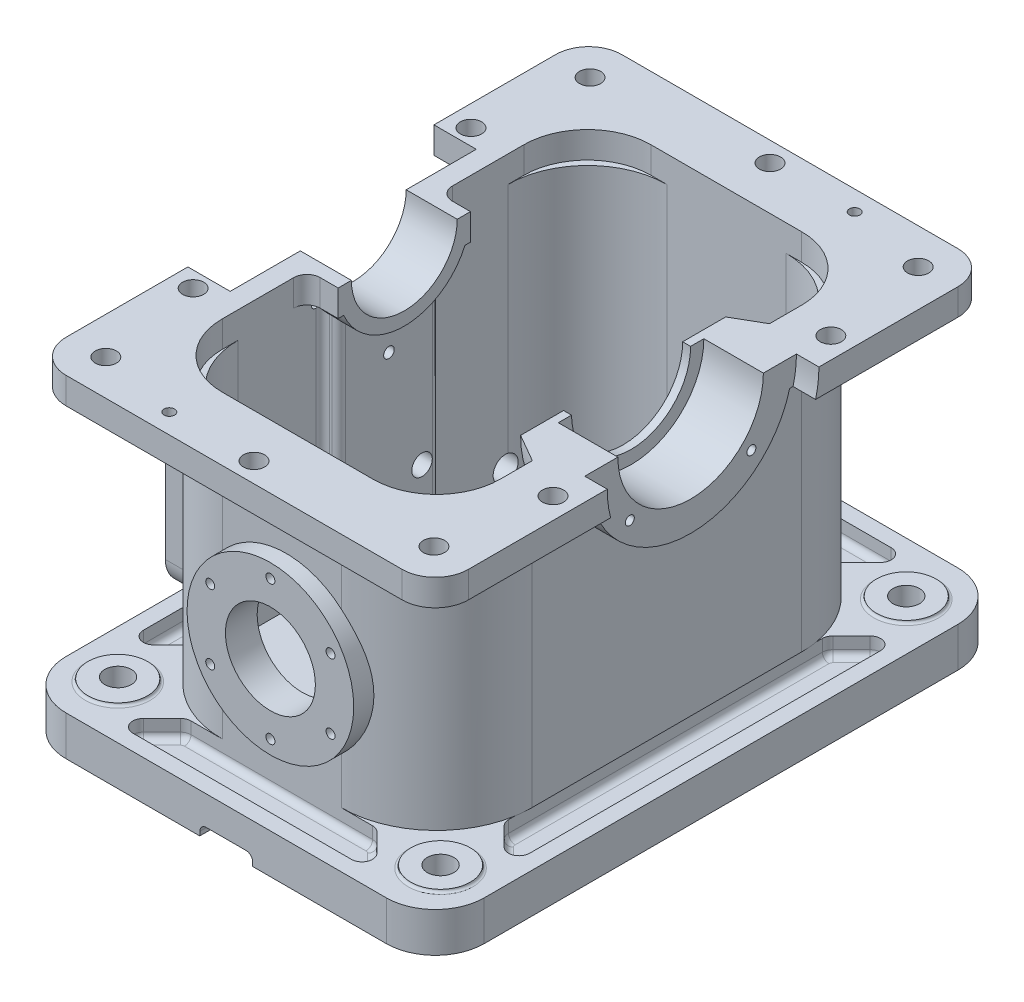
SolidWorks part; units mm, degrees
note: The reader was unsure of these and kept them because the rebuilt part matched: shared geometry of "草图44<2>".
ref_plane "前视基准面" through (0, 0, 0) normal (0, 0, 1) x (1, 0, 0)
ref_plane "上视基准面" through (0, 0, 0) normal (0, 1, 0) x (1, 0, 0)
ref_plane "右视基准面" through (0, 0, 0) normal (1, 0, 0) x (0, 0, -1)
sketch "草图1" plane through (0, 0, 0) normal (0, 1, 0) x (1, 0, 0)
  line L0 (0, 0) -> (316, 0)
  line L1 (316, 0) -> (316, 432)
  line L2 (316, 432) -> (0, 432)
  line L3 (0, 432) -> (0, 0)
extrude "凸台-拉伸1" add sketch "草图1" along normal blind 30
sketch "草图2" plane through (0, 30, 0) normal (0, 1, 0) x (1, 0, 0)
  circle A0 centre (36, 40) radius 22.5
  circle A1 centre (36, 392) radius 22.5
  circle A2 centre (280, 392) radius 22.5
  circle A3 centre (280, 40) radius 22.5
  point P12 (280, 0)
  point P13 (280, 432)
  point P14 (36, 0)
  point P15 (36, 432)
  point P16 (0, 40)
  point P17 (316, 40)
  point P18 (0, 392)
  point P19 (316, 392)
extrude "凸台-拉伸2" add sketch "草图2" along normal blind 2
sketch "草图3" plane through (0, 32, 0) normal (0, 1, 0) x (1, 0, 0)
  circle A0 centre (35.0597, 41.1667) radius 10
  circle A1 centre (36, 392) radius 10
  circle A2 centre (280, 40) radius 10
  circle A3 centre (280, 392) radius 10
extrude "切除-拉伸1" cut sketch "草图3" against normal through all
fillet "圆角1" radius 37 4 edges at (0, 15, -432) (0, 15, 0) (316, 15, 0) (316, 15, -432)
fillet "圆角3" radius 2 4 edges at (280, 30, -62.5) (36, 30, -17.5) (280, 30, -369.5) (36, 30, -414.5)
sketch "草图4" plane through (0, 30, 0) normal (0, 1, 0) x (1, 0, 0)
  line L0 (42, 334.603) -> (42, 97.397)
  line L1 (246.2599, 406.3431) -> (232.2599, 392.3431)
  line L2 (12, 348.603) -> (12, 83.397)
  line L3 (290.3431, 354.2599) -> (276.3431, 340.2599)
  line L4 (304, 348.603) -> (304, 83.397)
  line L5 (240.603, 420) -> (75.397, 420)
  line L6 (187.4957, 390) -> (187.4957, 390)
  line L7 (25.6569, 354.2599) -> (39.6569, 340.2599)
  line L8 (226.603, 390) -> (89.397, 390)
  line L9 (274, 334.603) -> (274, 97.397)
  line L10 (69.7401, 406.3431) -> (83.7401, 392.3431)
  line L11 (187.4957, 390) -> (37, 390) construction
  line L12 (246.2599, 406.3431) -> (209.0421, 369.1254) construction
  line L13 (226.603, 42) -> (89.397, 42)
  line L14 (304, 395) -> (304, 37) construction
  line L15 (274, 395) -> (274, 37) construction
  line L16 (316, 216) -> (0, 216) construction
  line L17 (316, 37) -> (316, 395) construction
  line L18 (0, 395) -> (0, 37) construction
  line L19 (158, 432) -> (158, 0) construction
  line L20 (279, 432) -> (37, 432) construction
  line L21 (37, 0) -> (279, 0) construction
  line L22 (240.603, 12) -> (75.397, 12)
  line L23 (69.7401, 25.6569) -> (83.7401, 39.6569)
  line L24 (240.603, 420) -> (37, 420) construction
  line L25 (290.3431, 77.7401) -> (276.3431, 91.7401)
  line L26 (246.2599, 25.6569) -> (232.2599, 39.6569)
  line L27 (25.6569, 77.7401) -> (39.6569, 91.7401)
  arc A0 (246.2599, 406.3431) -> (240.603, 420) centre (240.603, 412) ccw
  arc A1 (187.4957, 390) -> (187.4957, 390) centre (187.4957, 390) ccw
  arc A2 (232.2599, 392.3431) -> (226.603, 390) centre (226.603, 398) cw
  arc A3 (290.3431, 354.2599) -> (304, 348.603) centre (296, 348.603) cw
  arc A4 (276.3431, 340.2599) -> (274, 334.603) centre (282, 334.603) ccw
  arc A5 (39.6569, 340.2599) -> (42, 334.603) centre (34, 334.603) cw
  arc A6 (25.6569, 354.2599) -> (12, 348.603) centre (20, 348.603) ccw
  arc A7 (83.7401, 392.3431) -> (89.397, 390) centre (89.397, 398) ccw
  arc A8 (69.7401, 406.3431) -> (75.397, 420) centre (75.397, 412) cw
  arc A9 (69.7401, 25.6569) -> (75.397, 12) centre (75.397, 20) ccw
  arc A10 (83.7401, 39.6569) -> (89.397, 42) centre (89.397, 34) cw
  arc A11 (276.3431, 91.7401) -> (274, 97.397) centre (282, 97.397) cw
  arc A12 (290.3431, 77.7401) -> (304, 83.397) centre (296, 83.397) ccw
  arc A13 (232.2599, 39.6569) -> (226.603, 42) centre (226.603, 34) ccw
  arc A14 (246.2599, 25.6569) -> (240.603, 12) centre (240.603, 20) cw
  arc A15 (25.6569, 77.7401) -> (12, 83.397) centre (20, 83.397) cw
  arc A16 (39.6569, 91.7401) -> (42, 97.397) centre (34, 97.397) ccw
  point P24 (42, 216)
  point P46 (304, 216)
  point P48 (158, 420)
  point P54 (158, 390)
  point P56 (274, 216)
  point P78 (12, 216)
  dimension "D6" = 8
  dimension "D7" = 8
  dimension "D8" = 8
  dimension "D9" = 8
  dimension "D3" = 30
  dimension "D4" = 30
extrude "切除-拉伸2" cut sketch "草图4" against normal blind 14 contours A14 L26 A13 L13 A10 L23 A9 L22 | L27 A16 L0 A5 L7 A6 L2 A15 | L5 A8 L10 A7 L8 A2 L1 A0 | L9 A11 L25 A12 L4 A3 L3 A4
fillet "圆角4" radius 5 32 edges at (16.9385, 16, -76.0059) (12, 16, -216) (16.9385, 16, -355.9941) (32.6569, 16, -347.2599) (41.391, 16, -337.6645) (42, 16, -216) (41.391, 16, -94.3355) (32.6569, 16, -84.7401) (158, 16, -12) (68.0059, 16, -16.9385) (76.7401, 16, -32.6569) (86.3355, 16, -41.391) (158, 16, -42) (229.6645, 16, -41.391) (239.2599, 16, -32.6569) (247.9941, 16, -16.9385) (283.3431, 16, -347.2599) (299.0615, 16, -355.9941) (304, 16, -216) (299.0615, 16, -76.0059) (283.3431, 16, -84.7401) (274.609, 16, -94.3355) (274, 16, -216) (274.609, 16, -337.6645) (239.2599, 16, -399.3431) (229.6645, 16, -390.609) (158, 16, -390) (86.3355, 16, -390.609) (76.7401, 16, -399.3431) (68.0059, 16, -415.0615) (158, 16, -420) (247.9941, 16, -415.0615)
ref_plane "基准面1" through (0, 225, 0) normal (0, -1, 0) x (1, 0, 0)
sketch "草图5" plane through (0, 225, 0) normal (0, -1, 0) x (1, 0, 0)
  line L0 (158, -432) -> (158, 0) construction
  line L1 (279, -432) -> (37, -432) construction
  line L2 (37, 0) -> (279, 0) construction
  line L3 (0, -216) -> (316, -216) construction
  line L4 (0, -395) -> (0, -37) construction
  line L5 (316, -37) -> (316, -395) construction
  line L6 (263, -330) -> (263, -303.5)
  line L7 (53, -330) -> (53, -276)
  line L8 (101, -378) -> (215, -378)
  line L9 (101, -54) -> (215, -54)
  line L10 (6, -401) -> (6, -31)
  line L11 (31, -426) -> (285, -426)
  line L12 (310, -401) -> (310, -31)
  line L13 (31, -6) -> (285, -6)
  line L14 (53, -432) -> (53, 0) construction
  line L15 (0, -378) -> (316, -378) construction
  line L16 (263, -303.5) -> (242, -287.75)
  line L17 (0, -54) -> (316, -54) construction
  line L18 (242, -287.75) -> (242, -144.25)
  line L19 (263, -102) -> (263, -128.5)
  line L20 (263, -128.5) -> (242, -144.25)
  line L21 (76.6, -266) -> (63, -266)
  line L22 (101, -357) -> (215, -357) construction
  line L23 (74, -330) -> (74, -102) construction
  line L24 (101, -75) -> (215, -75) construction
  line L25 (242, -330) -> (242, -102) construction
  line L26 (76.6, -166) -> (76.6, -266)
  line L27 (76.6, -166) -> (63, -166)
  line L28 (263, -330) -> (263, -102) construction
  line L29 (53, -156) -> (53, -102)
  line L31 (53, -330) -> (53, -102) construction
  arc A1 (6, -401) -> (31, -426) centre (31, -401) ccw
  arc A2 (31, -6) -> (6, -31) centre (31, -31) ccw
  arc A3 (285, -6) -> (310, -31) centre (285, -31) cw
  arc A4 (310, -401) -> (285, -426) centre (285, -401) cw
  arc A5 (53, -330) -> (101, -378) centre (101, -330) ccw
  arc A6 (263, -330) -> (215, -378) centre (215, -330) cw
  arc A7 (215, -54) -> (263, -102) centre (215, -102) cw
  arc A8 (53, -102) -> (101, -54) centre (101, -102) cw
  arc A9 (53, -276) -> (63, -266) centre (63, -276) cw
  arc A10 (53, -156) -> (63, -166) centre (63, -156) ccw
  arc A13 (242, -330) -> (215, -357) centre (215, -330) cw construction
  arc A14 (74, -330) -> (101, -357) centre (101, -330) ccw construction
  arc A15 (74, -102) -> (101, -75) centre (101, -102) cw construction
  arc A16 (215, -75) -> (242, -102) centre (215, -102) cw construction
  point P65 (76.6, -216)
  point P74 (53, -166)
  dimension "D5" = 25
  dimension "D6" = 25
  dimension "D7" = 25
  dimension "D8" = 25
  dimension "D9" = 48
  dimension "D10" = 48
  dimension "D11" = 48
  dimension "D12" = 48
  dimension "D14" = 10
  dimension "D15" = 10
  dimension "D2" = 105
  dimension "D3" = 162
  dimension "D4" = 162
  dimension "D13" = 21
extrude "凸台-拉伸3" add sketch "草图5" against normal blind 20 separate body
sketch "草图6" plane through (0, 30, 0) normal (0, 1, 0) x (1, 0, 0)
  line L1 (263, 202) -> (263, 230)
  line L2 (65, 183) -> (65, 216)
  line L3 (65, 216) -> (65, 249)
  line L4 (60, 178) -> (58, 178)
  line L5 (60, 254) -> (58, 254)
  line L6 (53, 173) -> (53, 114)
  line L7 (113, 54) -> (203, 54)
  line L8 (263, 202) -> (263, 114)
  line L28 (275, 318) -> (275, 114)
  line L29 (113, 390) -> (203, 390)
  line L30 (41, 318) -> (41, 114)
  line L31 (113, 42) -> (203, 42)
  line L42 (263, 318) -> (263, 230)
  line L43 (113, 378) -> (203, 378)
  line L44 (53, 318) -> (53, 259)
  arc A0 (53, 114) -> (113, 54) centre (113, 114) ccw
  arc A1 (203, 54) -> (263, 114) centre (203, 114) ccw
  arc A2 (58, 254) -> (53, 259) centre (58, 259) cw
  arc A4 (60, 254) -> (65, 249) centre (60, 249) cw
  arc A5 (65, 183) -> (60, 178) centre (60, 183) cw
  arc A6 (53, 173) -> (58, 178) centre (58, 173) cw
  arc A20 (203, 42) -> (275, 114) centre (203, 114) ccw
  arc A21 (275, 318) -> (203, 390) centre (203, 318) ccw
  arc A22 (41, 318) -> (113, 390) centre (113, 318) cw
  arc A23 (41, 114) -> (113, 42) centre (113, 114) ccw
  arc A34 (263, 318) -> (203, 378) centre (203, 318) ccw
  arc A35 (53, 318) -> (113, 378) centre (113, 318) cw
  point P15 (251, 318)
  point P16 (251, 114)
  point P21 (65, 114)
  point P22 (65, 318)
  point P24 (0, 216)
  point P25 (316, 216)
  point P30 (0, 225)
  point P31 (316, 225)
  point P32 (0, 207)
  point P33 (316, 207)
  point P34 (235, 318)
  point P35 (235, 114)
  point P45 (251, 207)
  point P48 (77, 318)
  point P49 (77, 114)
  point P50 (53, 182)
  point P51 (316, 182)
  point P52 (53, 250)
  point P53 (316, 250)
  dimension "D3" = 5
ref_plane "基准面2" through (-5, 0, 0) normal (1, 0, 0) x (0, 0, -1)
sketch "草图7" plane through (-5, 0, 0) normal (1, 0, 0) x (0, 0, -1)
  circle A0 centre (316, 40) radius 17.5
  point P5 (432, 40)
  point P6 (261.659, 40)
  point P9 (316, 0)
  point P10 (316, 75.4539)
sketch "草图10" plane through (0, 0, 0) normal (-1, 0, 0) x (0, 0, 1)
  line L0 (-254, 30) -> (-249.5892, 36.1038)
  line L1 (-249.5892, 36.1038) -> (-182.0723, 36.1038)
  line L2 (-182.0723, 36.1038) -> (-178, 30)
  line L3 (-178, 30) -> (-178.4878, 30.1375)
  line L4 (-254, 25) -> (-178, 25)
  line L5 (-178, 25) -> (-178, 30)
  line L6 (-254, 25) -> (-254, 30)
  point P0 (-216, 0)
  point P1 (-216, 30)
  point P6 (-293.5905, 30)
  point P7 (-134.5219, 30)
  point P8 (-293.5905, 25)
  point P9 (-134.5219, 25)
  point P12 (-254, 0)
extrude "凸台-拉伸28" add sketch "草图6" along normal blind 195
ref_plane "基准面6" through (12, 30, -348.603) normal (0, 0, 1) x (1, 0, 0)
extrude "凸台-拉伸29" add sketch "草图7" along normal up to next
sketch "草图29" plane through (-5, 0, 0) normal (-1, 0, 0) x (0, 0, 1)
  point P0 (-316, 40)
hole_wizard "M20X1.5 螺纹孔的螺纹孔钻头2" positions "3D草图4" profile "草图30" hole size "M20X1.5" standard "GB"
sketch3d "3D草图4"
  point P0 (-5, 40, -316)
sketch "草图30" plane through (-5, 40, -316) normal (0, 1, 0) x (0, 0, 1)
  line L0 (0, 0) -> (0, 65.558)
  line L1 (0, 65.558) -> (9.25, 60)
  line L2 (9.25, 60) -> (9.25, 0)
  line L5 (9.25, 0) -> (0, 0)
  line L10 (0, 65.558) -> (-9.25, 60) construction
  line L11 (0, -6.35) -> (0, 107.95) construction
  dimension "孔直径" = 18.5
  dimension "孔深度" = 60
  dimension "导头角度" = 118
sketch "草图44" plane through (0, 0, -42) normal (0, 0, 1) x (1, 0, 0)
  circle A0 centre (161.3772, 112.6617) radius 63
extrude "凸台-拉伸31" add sketch "草图44" along normal blind 12
extrude "凸台-拉伸32" add sketch "草图44<2>" against normal up to next (12 mm away)
sketch "草图44<2>" plane through (0, 0, -42) normal (0, 0, 1) x (1, 0, 0) same geometry as "草图44"
sketch "草图45" plane through (0, 0, -30) normal (0, 0, 1) x (1, 0, 0)
  circle A0 centre (161.3772, 112.6617) radius 34
extrude "切除-拉伸13" cut sketch "草图45" against normal up to next
sketch "草图46" plane through (0, 0, -30) normal (0, 0, 1) x (1, 0, 0)
  point P3 (161.3772, 165.1617)
hole_wizard "M8 螺纹孔的螺纹孔钻头3" positions "3D草图5" profile "草图47" hole size "M8" standard "GB"
sketch3d "3D草图5"
  point P0 (161.3772, 165.1617, -30)
sketch "草图47" plane through (161.3772, 165.1617, -30) normal (1, 0, 0) x (0, -1, 0)
  line L0 (0, 0) -> (0, 17.0429)
  line L1 (0, 17.0429) -> (3.4, 15)
  line L2 (3.4, 15) -> (3.4, 0)
  line L5 (3.4, 0) -> (0, 0)
  line L10 (0, 17.0429) -> (-3.4, 15) construction
  line L11 (0, -6.35) -> (0, 107.95) construction
  dimension "孔直径" = 6.8
  dimension "孔深度" = 15
  dimension "导头角度" = 118
pattern_circular "阵列(圆周)1" count 6 over 360 about axis through (161.3772, 112.6617, 0) along (0, 0, 1) of "M8 螺纹孔的螺纹孔钻头3"
extrude "切除-拉伸3" cut sketch "草图10" against normal up to next
fillet "圆角7" radius 5 2 edges at (6, 25, -178) (6, 25, -254)
sketch "草图18" plane through (6, 0, 0) normal (-1, 0, 0) x (0, 0, 1)
  line L0 (-31, 245) -> (-401, 245) construction
  circle A0 centre (-216, 245) radius 80
ref_plane "基准面5" through (293, 0, 0) normal (-1, 0, 0) x (0, 0, 1)
sketch "草图27" plane through (293, 0, 0) normal (-1, 0, 0) x (0, 0, 1)
  line L0 (-138.5, 245) -> (-293.5, 245)
  arc A0 (-293.5, 245) -> (-138.5, 245) centre (-216, 245) ccw
extrude "凸台-拉伸27" add sketch "草图27" along normal blind 51
sketch "草图49" plane through (310, 0, 0) normal (1, 0, 0) x (0, 0, -1)
  line L0 (401, 245) -> (31, 245) construction
  line L1 (161, 245) -> (271, 245)
  arc A0 (161, 245) -> (271, 245) centre (216, 245) ccw
extrude "切除-拉伸14" cut sketch "草图49" against normal blind 62
chamfer "倒角4" distance 21 angle 30 1 edges at (263, 167.5, -216) first distance on face at (250.4261, 218.1036, -216)
sketch "草图50" plane through (242, 0, 0) normal (-1, 0, 0) x (0, 0, 1)
  line L0 (-293.5, 245) -> (-138.5, 245) construction
  circle A0 centre (-216, 245) radius 45
extrude "切除-拉伸15" cut sketch "草图50" against normal blind 62
sketch "草图52" plane through (293, 0, 0) normal (1, 0, 0) x (0, 0, -1)
  line L0 (141.1251, 225) -> (290.8749, 225)
  point P10 (170.0381, 199.0381)
  point P12 (261.9619, 199.0381)
hole_wizard "M8 螺纹孔的螺纹孔钻头4" positions "3D草图6" profile "草图53" hole size "M8" standard "GB"
sketch3d "3D草图6"
  point P0 (293, 199.0381, -170.0381)
  point P3 (293, 199.0381, -261.9619)
sketch "草图53" plane through (293, 199.0381, -170.0381) normal (0, 1, 0) x (0, 0, -1)
  line L0 (0, 0) -> (0, 17.0429)
  line L1 (0, 17.0429) -> (3.4, 15)
  line L2 (3.4, 15) -> (3.4, 0)
  line L5 (3.4, 0) -> (0, 0)
  line L10 (0, 17.0429) -> (-3.4, 15) construction
  line L11 (0, -6.35) -> (0, 107.95) construction
  dimension "孔直径" = 6.8
  dimension "孔深度" = 15
  dimension "导头角度" = 118
sketch "草图54" plane through (41, 0, 0) normal (-1, 0, 0) x (0, 0, 1)
  line L0 (-296, 245) -> (-136, 245)
  line L1 (-259, 33) -> (-173, 33)
  line L2 (-173, 33) -> (-173, 177.5389)
  line L3 (-259, 33) -> (-259, 177.5389)
  circle A0 centre (-216, 245) radius 80 construction
  arc A1 (-296, 245) -> (-259, 177.5389) centre (-216, 245) ccw
  arc A2 (-173, 177.5389) -> (-136, 245) centre (-216, 245) ccw
extrude "凸台-拉伸33" add sketch "草图54" along normal blind 3
sketch "草图55" plane through (6, 0, 0) normal (-1, 0, 0) x (0, 0, 1)
  line L0 (-31, 245) -> (-401, 245) construction
  line L1 (-296, 245) -> (-136, 245)
  line L2 (-293.4597, 225) -> (-138.5403, 225)
  arc A0 (-296, 245) -> (-293.4597, 225) centre (-216, 245) ccw
  arc A1 (-138.5403, 225) -> (-136, 245) centre (-216, 245) ccw
sketch "草图81" plane through (6, 0, 0) normal (-1, 0, 0) x (0, 0, 1)
  line L3 (-309, 245) -> (-309, 225)
  line L4 (-123, 245) -> (-123, 225)
  line L5 (-309, 245) -> (-123, 245)
  line L6 (-123, 225) -> (-309, 225)
extrude "切除-拉伸25" cut sketch "草图81" against normal blind 32
ref_plane "基准面9" through (33, 0, 0) normal (-1, 0, 0) x (0, 0, 1)
sketch "草图58" plane through (33, 0, 0) normal (-1, 0, 0) x (0, 0, 1)
  line L0 (-123, 155) -> (-123, 89)
  line L2 (-216, 0) -> (-136, 0)
  line L3 (-79, 155) -> (-79, 89)
  arc A2 (-123, 89) -> (-79, 89) centre (-101, 89) ccw
  arc A3 (-79, 155) -> (-123, 155) centre (-101, 155) ccw
extrude "凸台-拉伸35" add sketch "草图58" against normal up to next contours L3 A3 L0 A2
sketch "草图61" plane through (33, 0, 0) normal (-1, 0, 0) x (0, 0, 1)
  line L0 (-108.5, 89) -> (-108.5, 155)
  line L1 (-93.5, 89) -> (-93.5, 155)
  arc A0 (-93.5, 155) -> (-108.5, 155) centre (-101, 155) ccw
  arc A1 (-108.5, 89) -> (-93.5, 89) centre (-101, 89) ccw
extrude "切除-拉伸18" cut sketch "草图61" against normal blind 2
sketch "草图62" plane through (35, 0, 0) normal (-1, 0, 0) x (0, 0, 1)
  circle A0 centre (-101, 155) radius 7.5
  circle A1 centre (-101, 89) radius 7.5
extrude "切除-拉伸19" cut sketch "草图62" against normal up to next
sketch "草图63" plane through (33, 0, 0) normal (-1, 0, 0) x (0, 0, 1)
  point P2 (-101, 170)
  point P10 (-101, 74)
  point P12 (-116.5, 102)
  point P13 (-85.5, 102)
  point P14 (-116.5, 142)
  point P15 (-85.5, 142)
hole_wizard "M6 螺纹孔的螺纹孔钻头1" positions "3D草图7" profile "草图64" hole size "M6" standard "GB"
sketch3d "3D草图7"
  point P0 (33, 170, -101)
  point P3 (33, 142, -85.5)
  point P6 (33, 102, -85.5)
  point P9 (33, 74, -101)
  point P12 (33, 102, -116.5)
  point P15 (33, 142, -116.5)
sketch "草图64" plane through (33, 170, -101) normal (0, 1, 0) x (0, 0, 1)
  line L0 (0, 0) -> (0, 9.5022)
  line L1 (0, 9.5022) -> (2.5, 8)
  line L2 (2.5, 8) -> (2.5, 0)
  line L5 (2.5, 0) -> (0, 0)
  line L10 (0, 9.5022) -> (-2.5, 8) construction
  line L11 (0, -6.35) -> (0, 107.95) construction
  dimension "孔直径" = 5
  dimension "孔深度" = 8
  dimension "导头角度" = 118
sketch "草图65" plane through (38, 0, 0) normal (-1, 0, 0) x (0, 0, 1)
  line L0 (-259, 33) -> (-173, 33)
  point P8 (-216, 172)
  point P21 (-241, 147)
  point P22 (-191, 147)
  point P23 (-191, 86)
  point P24 (-241, 86)
  point P25 (-241, 47)
  point P26 (-191, 47)
hole_wizard "Ø8.0 (8) 直径孔1" positions "3D草图8" profile "草图66" hole size "Ø8.0" standard "GB"
sketch3d "3D草图8"
  point P0 (38, 172, -216)
sketch "草图66" plane through (38, 172, -216) normal (0, 1, 0) x (0, 0, 1)
  line L0 (0, 0) -> (0, 29.4024)
  line L1 (0, 29.4024) -> (4, 26.999)
  line L2 (4, 26.999) -> (4, 0)
  line L5 (4, 0) -> (0, 0)
  line L10 (0, 29.4024) -> (-4, 26.999) construction
  line L11 (0, -6.35) -> (0, 107.95) construction
  dimension "孔直径" = 8
  dimension "孔深度" = 26.999
  dimension "导头角度" = 118
hole_wizard "M12 螺纹孔的螺纹孔钻头1" positions "3D草图9" profile "草图67" hole size "M12" standard "GB"
sketch3d "3D草图9"
  point P0 (38, 47, -241)
  point P3 (38, 147, -241)
  point P6 (38, 147, -191)
  point P9 (38, 47, -191)
sketch "草图67" plane through (38, 47, -241) normal (0, 1, 0) x (0, 0, 1)
  line L0 (0, 0) -> (0, 21.0644)
  line L1 (0, 21.0644) -> (5.1, 18)
  line L2 (5.1, 18) -> (5.1, 0)
  line L5 (5.1, 0) -> (0, 0)
  line L10 (0, 21.0644) -> (-5.1, 18) construction
  line L11 (0, -6.35) -> (0, 107.95) construction
  dimension "孔直径" = 10.2
  dimension "孔深度" = 18
  dimension "导头角度" = 118
hole_wizard "M18 螺纹孔的螺纹孔钻头1" positions "3D草图10" profile "草图68" hole size "M18" standard "GB"
sketch3d "3D草图10"
  point P0 (38, 86, -241)
  point P3 (38, 86, -191)
sketch "草图68" plane through (38, 86, -241) normal (0, 1, 0) x (0, 0, 1)
  line L0 (0, 0) -> (0, 31.6557)
  line L1 (0, 31.6557) -> (7.75, 26.999)
  line L2 (7.75, 26.999) -> (7.75, 0)
  line L5 (7.75, 0) -> (0, 0)
  line L10 (0, 31.6557) -> (-7.75, 26.999) construction
  line L11 (0, -6.35) -> (0, 107.95) construction
  dimension "孔直径" = 15.5
  dimension "孔深度" = 26.999
  dimension "导头角度" = 118
sketch "草图69" plane through (0, 0, 0) normal (0, -1, 0) x (1, 0, 0)
  line L0 (52, -102) -> (52, -330)
  line L3 (215, -379) -> (101, -379)
  line L10 (264, -102) -> (264, -330)
  line L11 (215, -53) -> (101, -53)
  arc A4 (101, -379) -> (52, -330) centre (101, -330) cw
  arc A5 (264, -330) -> (215, -379) centre (215, -330) cw
  arc A6 (215, -53) -> (264, -102) centre (215, -102) cw
  arc A7 (52, -102) -> (101, -53) centre (101, -102) cw
extrude "切除-拉伸22" cut sketch "草图69" against normal blind 18
sketch "草图70" plane through (0, 0, 0) normal (0, 0, 1) x (1, 0, 0)
  line L0 (138, 0) -> (138, -7.8828)
  line L2 (178, 0) -> (178, 3)
  line L3 (138, 0) -> (138, 3)
  line L4 (143, 8) -> (173, 8)
  line L5 (138, -7.8828) -> (178, -7.8828)
  line L6 (178, 0) -> (178, -7.8828)
  arc A0 (138, 3) -> (143, 8) centre (143, 3) cw
  arc A1 (173, 8) -> (178, 3) centre (173, 3) cw
  dimension "D1" = 5
extrude "切除-拉伸23" cut sketch "草图70" against normal up to next
sketch "草图72" plane through (0, 245, 0) normal (0, 1, 0) x (1, 0, 0)
  line L2 (310, 161) -> (310, 271)
  point P0 (158, 411)
  point P1 (222, 411)
  point P4 (94, 21)
  point P5 (294, 111)
  point P6 (158, 21)
  point P7 (294, 321)
  point P9 (282, 33)
  point P10 (34, 33)
  point P13 (31, 33)
  point P14 (285, 33)
  point P15 (34, 399)
  point P18 (282, 399)
  point P23 (22, 321)
  point P24 (22, 111)
hole_wizard "Ø8.0 (8) 直径孔2" positions "3D草图11" profile "草图73" hole size "Ø8.0" standard "GB" end condition up to next
sketch3d "3D草图11"
  point P0 (94, 245, -21)
  point P3 (222, 245, -411)
sketch "草图73" plane through (94, 245, -21) normal (1, 0, 0) x (0, 0, 1)
  line L0 (0, 0) -> (0, 20)
  line L1 (0, 20) -> (4, 20)
  line L2 (4, 20) -> (4, 0)
  line L5 (4, 0) -> (0, 0)
  line L11 (0, -6.35) -> (0, 107.95) construction
  dimension "通孔孔直径" = 8
  dimension "通孔孔深度" = 20
hole_wizard "Ø16.0 (16) 直径孔1" positions "3D草图13" profile "草图75" hole size "Ø16.0" standard "GB" end condition up to next
sketch3d "3D草图13"
  point P0 (34, 245, -33)
  point P3 (158, 245, -21)
  point P6 (282, 245, -33)
  point P9 (294, 245, -111)
  point P12 (22, 245, -111)
  point P15 (22, 245, -321)
  point P18 (34, 245, -399)
  point P21 (158, 245, -411)
  point P24 (282, 245, -399)
  point P27 (294, 245, -321)
sketch "草图75" plane through (34, 245, -33) normal (1, 0, 0) x (0, 0, 1)
  line L0 (0, 0) -> (0, 20)
  line L1 (0, 20) -> (8, 20)
  line L2 (8, 20) -> (8, 0)
  line L5 (8, 0) -> (0, 0)
  line L11 (0, -6.35) -> (0, 107.95) construction
  dimension "通孔孔直径" = 16
  dimension "通孔孔深度" = 20
sketch "草图76" plane through (263, 0, 0) normal (-1, 0, 0) x (0, 0, 1)
  circle A0 centre (-216, 102) radius 9
extrude "凸台-拉伸36" add sketch "草图76" along normal blind 16
fillet "圆角21" radius 5 2 edges at (263, 102, -207) (247, 102, -207)
sketch "草图80" plane through (310, 0, 0) normal (1, 0, 0) x (0, 0, -1)
  line L1 (296, 245) -> (136, 245)
  line L2 (293.4597, 225) -> (138.5403, 225)
  line L3 (296, 225) -> (136, 225) construction
  arc A0 (136, 245) -> (138.5403, 225) centre (216, 245) ccw
  arc A1 (293.4597, 225) -> (296, 245) centre (216, 245) ccw
  dimension "D1" = 20
extrude "切除-拉伸24" cut sketch "草图80" against normal blind 17
sketch "草图82" plane through (38, 0, 0) normal (-1, 0, 0) x (0, 0, 1)
  line L0 (-123, 245) -> (-309, 245) construction
  circle A0 centre (-216, 245) radius 40
sketch "草图83" plane through (38, 0, 0) normal (-1, 0, 0) x (0, 0, 1)
  point P3 (-172.6987, 220)
  point P4 (-259.3013, 220)
  point P5 (-216, 195)
sketch "草图85" plane through (38, 0, 0) normal (-1, 0, 0) x (0, 0, 1)
  line L0 (-266, 245) -> (-166, 245)
  arc A0 (-266, 245) -> (-166, 245) centre (-216, 245) ccw
extrude "凸台-拉伸37" add sketch "草图85" against normal up to surface (38.6 mm away) up to face at (76.6, 235, -216)
extrude "切除-拉伸27" cut sketch "草图82" against normal blind 59
hole_wizard "M8 螺纹孔的螺纹孔钻头6" positions "3D草图15" profile "草图86" hole size "M8" standard "GB"
sketch3d "3D草图15"
  point P0 (38, 220, -259.3013)
  point P3 (38, 195, -216)
  point P6 (38, 220, -172.6987)
sketch "草图86" plane through (38, 220, -259.3013) normal (0, 1, 0) x (0, 0, 1)
  line L0 (0, 0) -> (0, 22.0429)
  line L1 (0, 22.0429) -> (3.4, 20)
  line L2 (3.4, 20) -> (3.4, 0)
  line L5 (3.4, 0) -> (0, 0)
  line L10 (0, 22.0429) -> (-3.4, 20) construction
  line L11 (0, -6.35) -> (0, 107.95) construction
  dimension "孔直径" = 6.8
  dimension "孔深度" = 20
  dimension "导头角度" = 118
ref_plane "基准面10" through (0, 0, -216) normal (0, 0, -1) x (-1, 0, 0)
ref_plane "基准面11" through (158, 0, 0) normal (-1, 0, 0) x (0, 0, 1)
